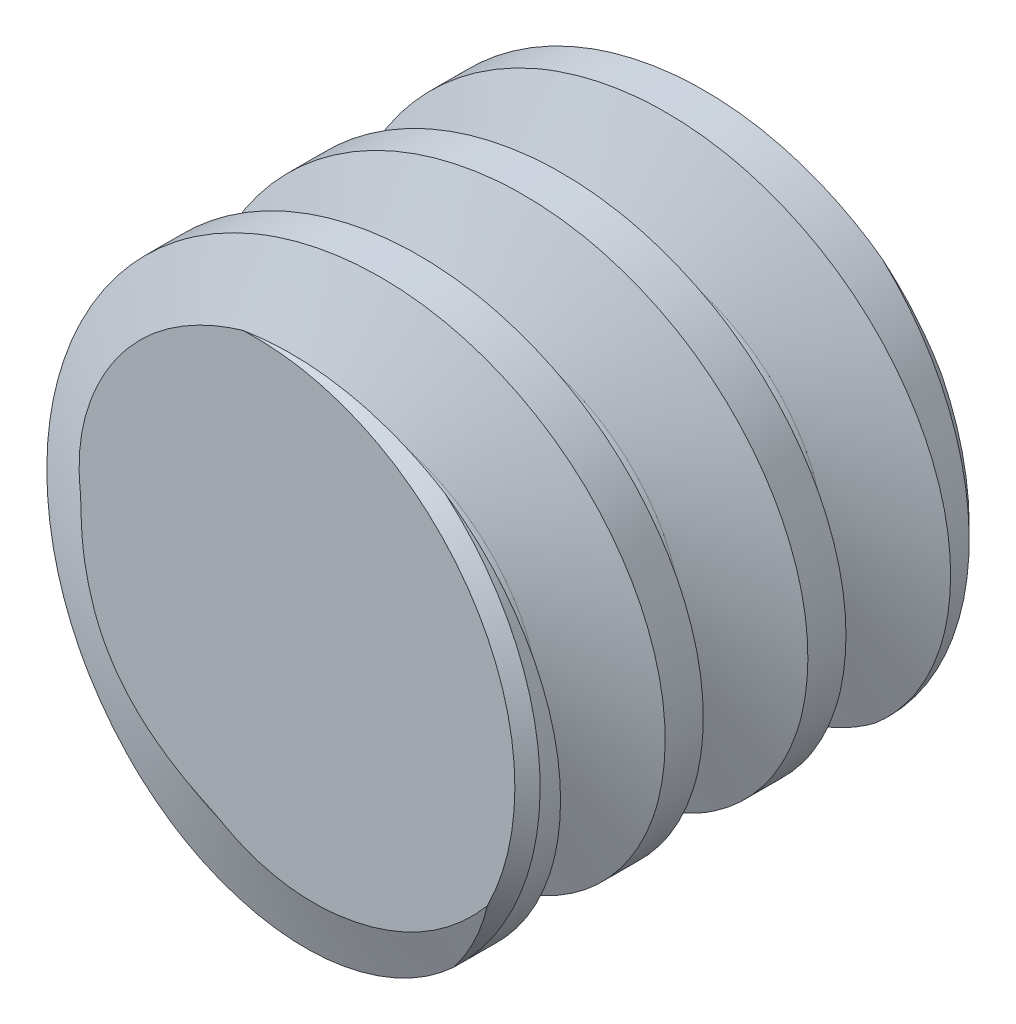
SolidWorks part; units mm, degrees
note: '?' marks a value the reader was unsure of.
ref_plane "Спереди" through (0, 0, 0) normal (0, 0, 1) x (1, 0, 0)
ref_plane "Сверху" through (0, 0, 0) normal (0, 1, 0) x (1, 0, 0)
ref_plane "Справа" through (0, 0, 0) normal (1, 0, 0) x (0, 0, -1)
ref_axis "Ось1" through (0, 0, 55) along (0, 0, -1)?
sketch "SketchRevolveWorm01" plane through (0, 0, 0) normal (1, 0, 0) x (0, 0, -1)
  line L0 (0, 0) -> (1, 0) construction
  line L1 (5, 0) -> (5, 5.722)
  line L2 (5, 5.722) -> (4.722, 6)
  line L3 (4.722, 6) -> (-4.722, 6)
  line L4 (-4.722, 6) -> (-5, 5.722)
  line L5 (-5, 5.722) -> (-5, 0)
  line L6 (-5, 0) -> (5, 0)
  dimension "ChamferX" = 0.278
  dimension "ChamferY" = 0.278
  dimension "OutsideDiameter" = 6
  dimension "WormLength" = 10
revolve "Worm01" add sketch "SketchRevolveWorm01" angle 360 about L0
ref_plane "HelixPlaneWorm01" through (0, 0, 9.4248) normal (0, 0, 1) x (1, 0, 0)
sketch "SketchHelixWorm01" plane through (0, 0, 9.4248) normal (0, 0, 1) x (1, 0, 0)
  circle A0 centre (0, 0) radius 5
  dimension "PitchDiameter" = 10
curve "GearHelixWorm01" pitch 3.1416 height 18.8496 turns 6
sketch "SketchToothWorm01" plane through (0, 0, 0) normal (0, 1, 0) x (1, 0, 0)
  line L0 (6.25, -8.182) -> (3.9469, -9.0248)
  line L1 (3.75, -9.3065) -> (3.75, -9.5431)
  line L2 (3.9469, -9.8248) -> (6.25, -10.6676)
  line L3 (6.25, -10.6676) -> (6.25, -8.182)
  arc A0 (3.9469, -9.0248) -> (3.75, -9.3065) centre (4.05, -9.3065) ccw
  arc A1 (3.75, -9.5431) -> (3.9469, -9.8248) centre (4.05, -9.5431) ccw
sweep "ToothCutWorm01" cut profiles "SketchToothWorm01" path "GearHelixWorm01"
sketch "BoreRevolveSketch" plane through (0, 0, 0) normal (1, 0, 0) x (0, 0, -1)
  line L0 (-5, 0) -> (5, 0)
  line L1 (5, 0) -> (5, 2.5)
  line L2 (5, 2.5) -> (-5, 2.5)
  line L3 (-5, 2.5) -> (-5, 0)
  dimension "TaperSide1" = 2.5
  dimension "TaperSide2" = 2.5
sketch "AuxiliarySketchWorm01" plane through (0, 0, 0) normal (0, 0, 1) x (1, 0, 0)
  circle A0 centre (0, 0) radius 5 construction
  dimension "PitchDiameter" = 10
